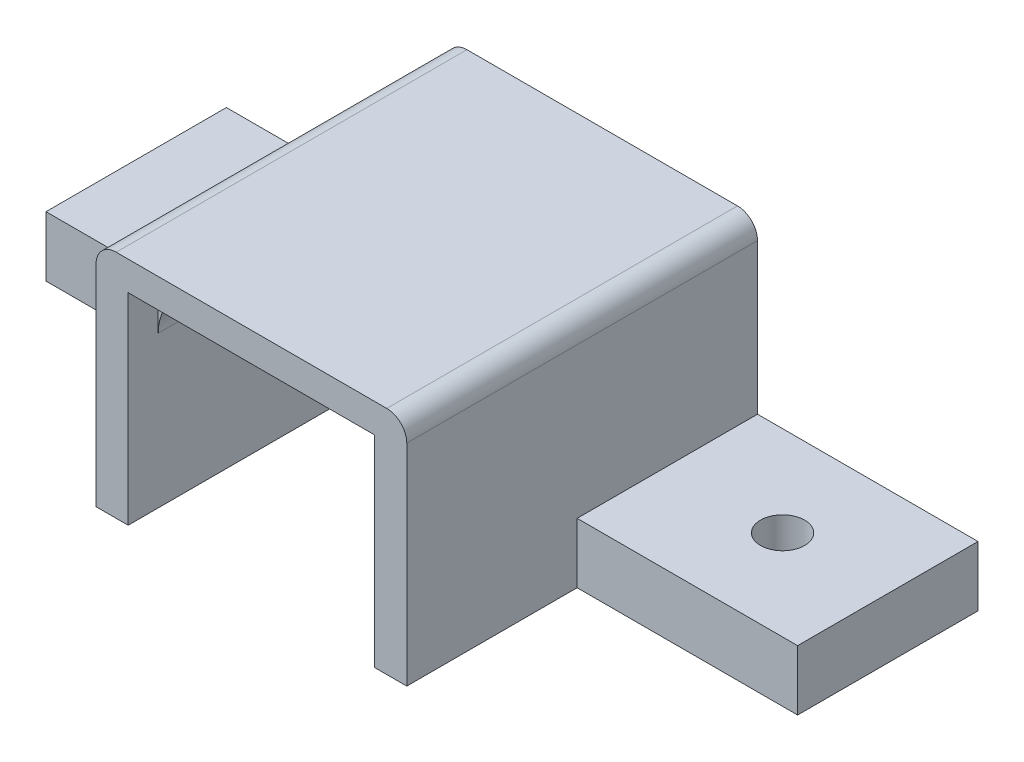
SolidWorks part; units mm, degrees
ref_plane "Alzado" through (0, 0, 0) normal (0, 0, 1) x (1, 0, 0)
ref_plane "Planta" through (0, 0, 0) normal (0, 1, 0) x (1, 0, 0)
ref_plane "Vista lateral" through (0, 0, 0) normal (1, 0, 0) x (0, 0, -1)
sketch "Croquis1" plane through (0, 0, 0) normal (0, 1, 0) x (1, 0, 0)
  line L1 (-7.75, -8.75) -> (7.75, -8.75)
  line L2 (-7.75, -8.75) -> (-7.75, 8.75)
  line L3 (-7.75, 8.75) -> (7.75, 8.75)
  line L4 (7.75, -8.75) -> (7.75, 8.75)
  line L5 (-7.75, -8.75) -> (7.75, 8.75) construction
  line L6 (-7.75, 8.75) -> (7.75, -8.75) construction
  point P0 (0, 0)
  dimension "D1" = 15.5
  dimension "D2" = 17.5
extrude "Saliente-Extruir1" add sketch "Croquis1" along normal blind 11.5 contours L1 L4 L3 L2
sketch "Croquis2" plane through (0, 0, 8.75) normal (0, 0, 1) x (1, 0, 0)
  line L0 (-7.75, 0) -> (-6.15, 0)
  line L1 (-7.75, 0) -> (7.75, 0) construction
  line L2 (-7.75, 11.5) -> (7.75, 11.5) construction
  line L3 (-6.15, 0) -> (6.15, 0)
  line L4 (-6.15, 0) -> (-6.15, 10.05)
  line L5 (-6.15, 10.05) -> (6.15, 10.05)
  line L6 (6.15, 0) -> (6.15, 10.05)
  line M2 (-7.75, 0) -> (7.75, 0)
  dimension "D1" = 1.45
  dimension "D2" = 1.6
  dimension "D3" = 1.6
extrude "Cortar-Extruir1" cut sketch "Croquis2" against normal through all contours L6 L5 L4 M2 region at (0, 5.025, 8.75)
fillet "Redondeo1" radius 1 2 edges at (7.75, 11.5, 0) (-7.75, 11.5, 0)
sketch "Croquis3" plane through (7.75, 0, 0) normal (1, 0, 0) x (0, 0, -1)
  line L1 (8.75, 0) -> (-0.25, 0)
  line L2 (8.75, 0) -> (8.75, 3)
  line L3 (8.75, 3) -> (-0.25, 3)
  line L4 (-0.25, 0) -> (-0.25, 3)
  dimension "D1" = 9
  dimension "D2" = 3
extrude "Saliente-Extruir4" add sketch "Croquis3" along normal blind 11 separate body
sketch "Croquis12" plane through (0, 3, 0) normal (0, 1, 0) x (1, 0, 0)
  line L1 (-6.15, 8.75) -> (6.15, 8.75) construction
  line L2 (18.75, 8.75) -> (7.75, 8.75) construction
  circle A0 centre (13.5, 4.25) radius 1.1
  point P3 (0, 8.75)
  dimension "D1" = 2.2
  dimension "D2" = 4.5
  dimension "D3" = 13.5
extrude "Cortar-Extruir7" cut sketch "Croquis12" against normal through all
sketch "Croquis13" plane through (0, 11.5, 0) normal (0, 1, 0) x (1, 0, 0)
  line L0 (0, 8.75) -> (0, -8.75)
  line L1 (0, 8.75) -> (-18.0784, 8.75)
  line L2 (0, -8.75) -> (-18.0784, -8.75)
  line L3 (-18.0784, 8.75) -> (-18.0784, -8.75)
  line L4 (-6.75, 8.75) -> (6.75, 8.75) construction
  line L5 (-6.75, -8.75) -> (6.75, -8.75) construction
extrude "Cortar-Extruir8" cut sketch "Croquis13" against normal through all
mirror "Simetría2" about plane through (0, 0, -8.75) normal (1, 0, 0) of "Saliente-Extruir1", "Cortar-Extruir1", "Redondeo1", "Saliente-Extruir4", "Cortar-Extruir7"
combine bodies "Combinar3" operation type add bodies to combine 119 117
fillet "Redondeo6" radius 2 2 edges at (-6.15, 10.05, 0) (6.15, 10.05, 0)
sketch "Croquis15" plane through (0, 0, 0) normal (0, -1, 0) x (-1, 0, 0)
  line L0 (0, 0.75) -> (0, -8.75)
  line L1 (-6.15, 8.75) -> (6.15, 8.75)
  line L2 (-6.15, 8.75) -> (-6.15, -8.75)
  line L3 (-6.15, -8.75) -> (6.15, -8.75)
  line L4 (6.15, 8.75) -> (6.15, -8.75)
  line L5 (-6.15, 8.75) -> (6.15, 8.75)
  line L6 (-6.15, 8.75) -> (-6.15, 0.75)
  line L7 (-6.15, 0.75) -> (6.15, 0.75)
  line L8 (6.15, 8.75) -> (6.15, 0.75)
  line L10 (-6.15, 0.75) -> (0, 0.75)
  line L11 (-6.15, 0.75) -> (-6.15, -0.45)
  line L12 (-6.15, -0.45) -> (0, -0.45)
  line L13 (0, 0.75) -> (0, -0.45)
  line L14 (-6.15, -0.45) -> (0, -0.45)
  line L15 (-6.15, -0.45) -> (-6.15, -2.25)
  line L16 (-6.15, -2.25) -> (0, -2.25)
  line L17 (0, -0.45) -> (0, -2.25)
  line L18 (-6.15, -2.25) -> (0, -2.25)
  line L19 (-6.15, -2.25) -> (-6.15, -3.25)
  line L20 (-6.15, -3.25) -> (0, -3.25)
  line L21 (0, -2.25) -> (0, -3.25)
  line L22 (-6.15, -3.25) -> (0, -3.25)
  line L23 (-6.15, -3.25) -> (-6.15, -7.25)
  line L24 (-6.15, -7.25) -> (0, -7.25)
  line L25 (0, -3.25) -> (0, -7.25)
  line M2 (-6.15, -8.75) -> (-6.15, 8.75)
  dimension "D1" = 8
  dimension "D2" = 1.2
  dimension "D3" = 1.8
  dimension "D4" = 1
  dimension "D5" = 4
extrude "Cortar-Extruir10" cut sketch "Croquis15" against normal up to surface (10.05 mm away) contours L2 L12 L0 L7 | L2 L20 L0 L16 | L24 L3 L0 M2 | L7 L0 L3 L4 region at (-3.075, 0, 4) region at (3.075, 0, -0.15) region at (3.075, 0, 2.75) region at (3.075, 0, 8) up to face at (0, 10.05, 0)
sketch "Croquis17" plane through (0, 10.05, 0) normal (0, -1, 0) x (1, 0, 0)
  line L0 (4.15, 7.25) -> (-6.15, 7.25) construction
  line L1 (-6.15, 8.75) -> (-6.15, -0.75) construction
  line L2 (4.15, 3.25) -> (-6.15, 3.25) construction
  line L4 (-6.15, 7.25) -> (-3.65, 7.25)
  line L5 (-6.15, 7.25) -> (-6.15, 3.25)
  line L6 (-6.15, 3.25) -> (-3.65, 3.25)
  line L7 (-3.65, 7.25) -> (-3.65, 3.25)
  dimension "D1" = 2.5
extrude "Saliente-Extruir6" add sketch "Croquis17" along normal blind 2.5
sketch "Croquis19" plane through (0, 0, 7.25) normal (0, 0, 1) x (1, 0, 0)
  circle A0 centre (-3.65, 7.55) radius 2.5
extrude "Cortar-Extruir12" cut sketch "Croquis19" against normal up to surface (4 mm away) up to face at (-4.9, 8.8, 3.25)
sketch "Croquis20" plane through (0, 10.05, 0) normal (0, -1, 0) x (1, 0, 0)
  line L1 (6.15, 0.45) -> (4.15, 0.45)
  line L2 (6.15, 0.45) -> (6.15, 2.25)
  line L3 (6.15, 2.25) -> (4.15, 2.25)
  line L4 (4.15, 0.45) -> (4.15, 2.25)
extrude "Cortar-Extruir13" cut sketch "Croquis20" along normal up to vertex (2 mm away) up to point (6.15, 8.05, 0.45)
